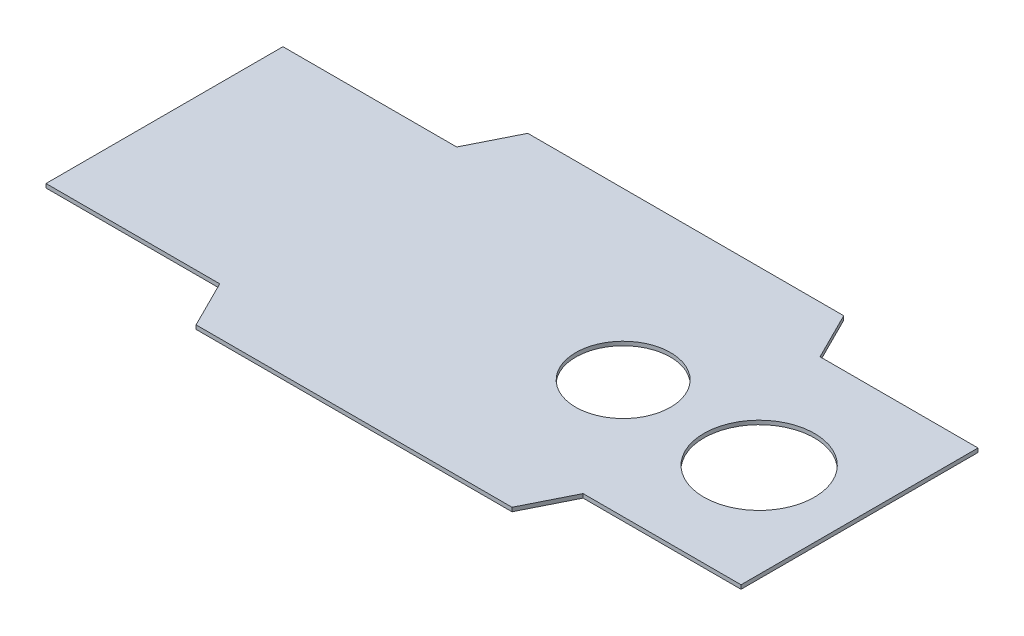
SolidWorks part; units mm, degrees
ref_plane "Front Plane" through (0, 0, 0) normal (0, 0, 1) x (1, 0, 0)
ref_plane "Top Plane" through (0, 0, 0) normal (0, 1, 0) x (1, 0, 0)
ref_plane "Right Plane" through (0, 0, 0) normal (1, 0, 0) x (0, 0, -1)
sketch "Sketch3" plane through (0, 0, 0) normal (0, 1, 0) x (1, 0, 0)
  line L0 (-279.4, 95.25) -> (-139.7, 95.25)
  line L1 (-279.4, -133.35) -> (279.4, -133.35) construction
  line L2 (-279.4, -133.35) -> (-279.4, 133.35) construction
  line L3 (-279.4, 133.35) -> (279.4, 133.35) construction
  line L4 (279.4, -133.35) -> (279.4, 133.35) construction
  line L5 (-279.4, -133.35) -> (279.4, 133.35) construction
  line L6 (-279.4, 133.35) -> (279.4, -133.35) construction
  line L7 (-279.4, -95.25) -> (279.4, -95.25) construction
  line L8 (-279.4, -95.25) -> (-279.4, 95.25) construction
  line L9 (-279.4, 95.25) -> (279.4, 95.25) construction
  line L10 (279.4, -95.25) -> (279.4, 95.25) construction
  line L13 (-139.7, 95.25) -> (-120.65, 133.35)
  line L14 (-120.65, 133.35) -> (133.35, 133.35)
  line L15 (133.35, 133.35) -> (152.4, 95.25)
  line L16 (152.4, 95.25) -> (279.4, 95.25)
  line L17 (-279.4, 95.25) -> (-279.4, -95.25)
  line L18 (279.4, 95.25) -> (279.4, -95.25)
  line L19 (-279.4, 0) -> (279.4, 0) construction
  line L20 (152.4, -95.25) -> (279.4, -95.25)
  line L21 (133.35, -133.35) -> (152.4, -95.25)
  line L22 (-120.65, -133.35) -> (133.35, -133.35)
  line L23 (-139.7, -95.25) -> (-120.65, -133.35)
  line L24 (-279.4, -95.25) -> (-139.7, -95.25)
  point P0 (0, 0)
  point P6 (0, 0)
  dimension "D1" = 266.7
  dimension "D2" = 558.8
  dimension "D3" = 190.5
  dimension "D4" = 127
  dimension "D5" = 139.7
  dimension "D6" = 254
extrude "Boss-Extrude1" add sketch "Sketch3" along normal mid plane 3.175
sketch "Sketch5" plane through (0, -1.5875, 0) normal (0, -1, 0) x (1, 0, 0)
  line L0 (-202.3532, 0) -> (279.4, 0) construction
  line L1 (-63.5, 25.4) -> (76.2, 25.4)
  line L2 (-63.5, 25.4) -> (-63.5, 88.9)
  line L3 (-63.5, 88.9) -> (76.2, 88.9)
  line L4 (76.2, 25.4) -> (76.2, 88.9)
  line L5 (-63.5, 25.4) -> (76.2, 88.9) construction
  line L6 (-63.5, 88.9) -> (76.2, 25.4) construction
  line L7 (279.4, 95.25) -> (279.4, -95.25) construction
  line L8 (-120.65, 133.35) -> (133.35, 133.35) construction
  line L9 (-120.65, 133.35) -> (133.35, 133.35) construction
  line L10 (6.35, 133.35) -> (6.35, 88.9) construction
  line L11 (-63.5, -88.9) -> (76.2, -88.9)
  line L12 (76.2, -25.4) -> (76.2, -88.9)
  line L13 (-63.5, -25.4) -> (76.2, -25.4)
  line L14 (-63.5, -25.4) -> (-63.5, -88.9)
  point P4 (6.35, 57.15)
  dimension "D1" = 63.5
  dimension "D2" = 139.7
  dimension "D3" = 44.45
sketch "Sketch6" plane through (0, 1.5875, 0) normal (0, 1, 0) x (1, 0, 0)
  line L0 (-279.4, 95.25) -> (-139.7, 95.25) construction
  line L1 (-120.65, 133.35) -> (-139.7, 95.25) construction
  line L2 (-139.7, 95.25) -> (-279.4, 95.25) construction
  line L3 (-139.7, 95.25) -> (-120.65, 133.35) construction
  line L4 (-120.65, 133.35) -> (133.35, 133.35) construction
  line L5 (133.35, 133.35) -> (152.4, 95.25) construction
  line L6 (152.4, 95.25) -> (279.4, 95.25) construction
  line L7 (279.4, 95.25) -> (279.4, -95.25) construction
  line L8 (279.4, -95.25) -> (152.4, -95.25) construction
  line L9 (133.35, -133.35) -> (152.4, -95.25) construction
  line L10 (152.4, -95.25) -> (279.4, -95.25) construction
  line L11 (152.4, -95.25) -> (133.35, -133.35) construction
  line L12 (133.35, -133.35) -> (-120.65, -133.35) construction
  line L13 (-120.65, -133.35) -> (-139.7, -95.25) construction
  line L14 (-139.7, -95.25) -> (-279.4, -95.25) construction
  line L15 (-279.4, -95.25) -> (-279.4, 95.25) construction
  line L16 (-276.225, 92.075) -> (-137.7377, 92.075)
  line L17 (-137.7377, 92.075) -> (-118.6877, 130.175)
  line L18 (-118.6877, 130.175) -> (131.3877, 130.175)
  line L19 (131.3877, 130.175) -> (150.4377, 92.075)
  line L20 (150.4377, 92.075) -> (276.225, 92.075)
  line L21 (276.225, 92.075) -> (276.225, -92.075)
  line L22 (276.225, -92.075) -> (150.4377, -92.075)
  line L23 (150.4377, -92.075) -> (131.3877, -130.175)
  line L24 (131.3877, -130.175) -> (-118.6877, -130.175)
  line L25 (-118.6877, -130.175) -> (-137.7377, -92.075)
  line L26 (-137.7377, -92.075) -> (-276.225, -92.075)
  line L27 (-276.225, -92.075) -> (-276.225, 92.075)
  dimension "D1" = 3.175
sketch "Sketch7" plane through (0, 1.5875, 0) normal (0, 1, 0) x (1, 0, 0)
  circle A1 centre (89.3496, 0) radius 38.1
  circle A3 centre (203.5007, -4.7849) radius 44.45
  dimension "D1" = 76.2
extrude "Cut-Extrude1" cut sketch "Sketch7" against normal blind 20.32
